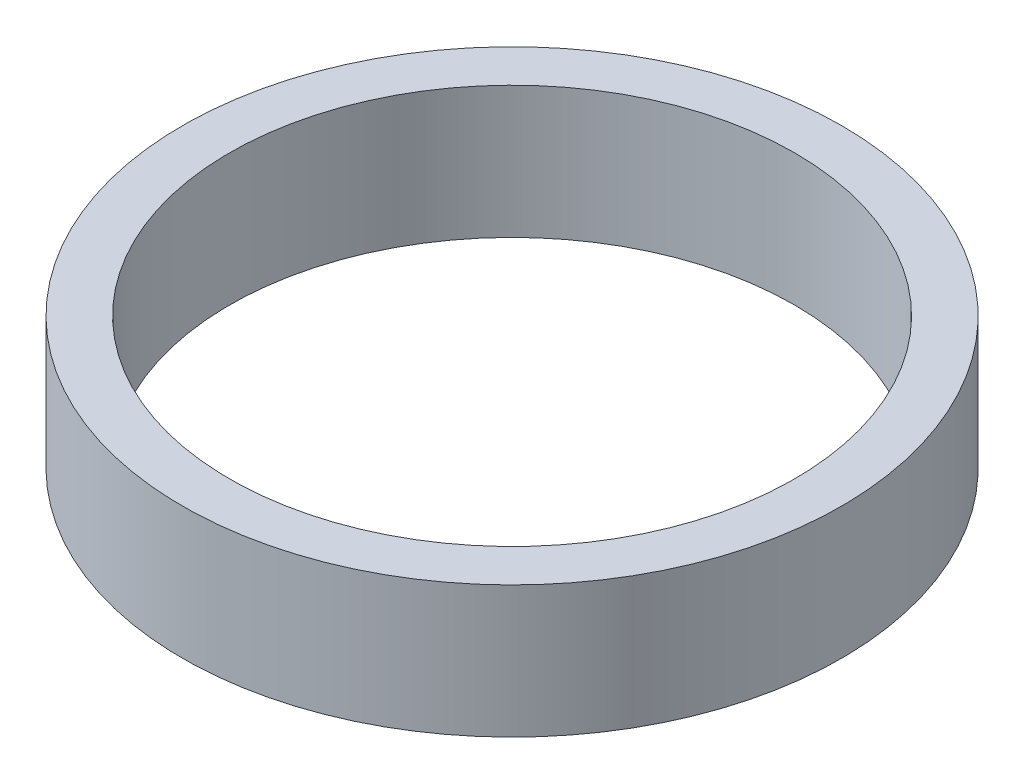
SolidWorks part; units mm, degrees
ref_plane "Front Plane" through (0, 0, 0) normal (0, 0, 1) x (1, 0, 0)
ref_plane "Top Plane" through (0, 0, 0) normal (0, 1, 0) x (1, 0, 0)
ref_plane "Right Plane" through (0, 0, 0) normal (1, 0, 0) x (0, 0, -1)
sketch "Sketch1" plane through (0, 0, 0) normal (0, 1, 0) x (1, 0, 0)
  circle A0 centre (0, 0) radius 52.5
  dimension "FLANGE_OD" = 105
extrude "Boss-Extrude1" add sketch "Sketch1" along normal blind 21
sketch "Sketch2" plane through (0, 0, 0) normal (0, 1, 0) x (1, 0, 0)
  circle A0 centre (0, 0) radius 45
  dimension "BORE_D" = 90
extrude "Cut-Extrude1" cut sketch "Sketch2" along normal through all
sketch "Sketch3" plane through (0, 21, 0) normal (0, 1, 0) x (1, 0, 0)
  circle A0 centre (0, 0) radius 24.4634 construction
  circle A1 centre (-24.4634, 0) radius 1.5
  dimension "BOLT_D" = 3
  dimension "BOLT_PCD" = 48.9268
extrude "Cut-Extrude2" cut sketch "Sketch3" against normal blind 17.9887 rebuild error yes
pattern_circular "CirPattern1" count 4 over 360 rebuild error yes
